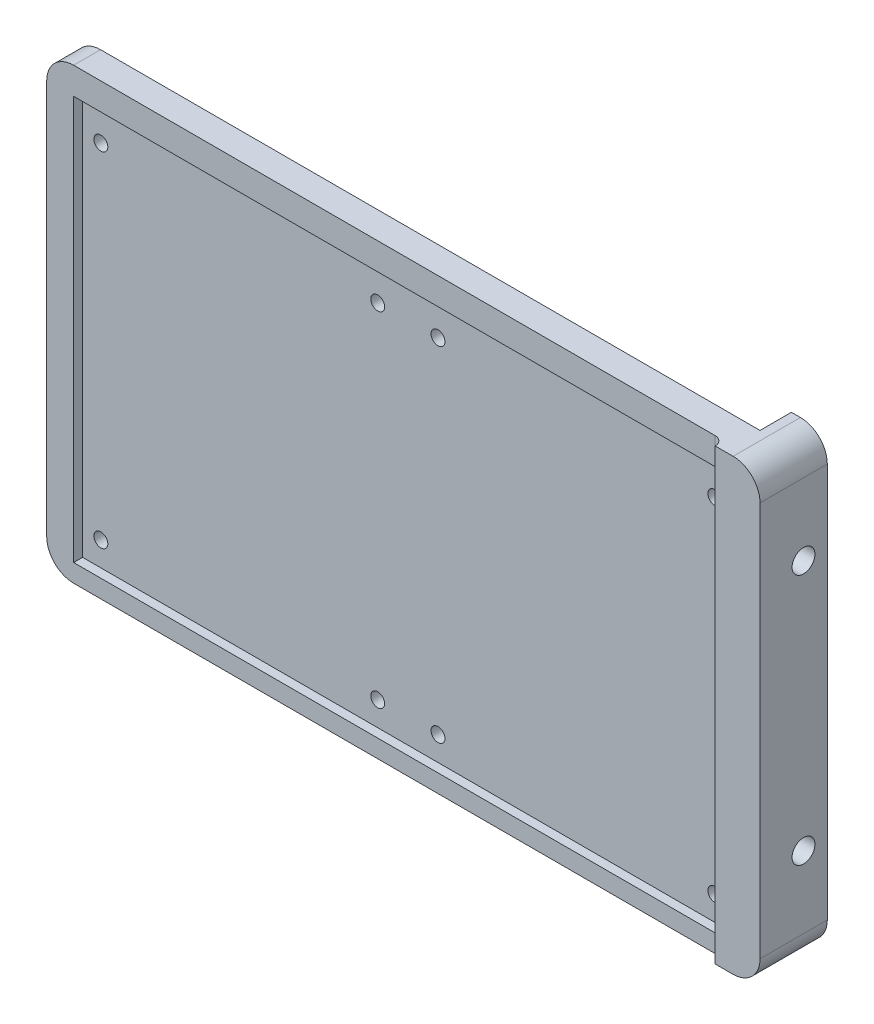
SolidWorks part; units mm, degrees
ref_plane "Front Plane" through (0, 0, 0) normal (0, 0, 1) x (1, 0, 0)
ref_plane "Top Plane" through (0, 0, 0) normal (0, 1, 0) x (1, 0, 0)
ref_plane "Right Plane" through (0, 0, 0) normal (1, 0, 0) x (0, 0, -1)
sketch "Sketch1" plane through (0, 0, 0) normal (0, 0, 1) x (1, 0, 0)
  line L0 (0, 0) -> (145, 0)
  line L1 (145, 0) -> (145, 100)
  line L2 (145, 100) -> (0, 100)
  line L3 (0, 100) -> (0, 0)
  line L4 (0, 0) -> (4.07, 0)
  line L5 (145, 0) -> (140.93, 0)
  line L6 (140.93, 0) -> (140.93, 100)
  line L7 (4.07, 0) -> (4.07, 100)
  line L8 (0, 100) -> (69.85, 100)
  line L9 (69.85, 100) -> (69.85, 0)
  line L10 (145, 100) -> (75.15, 100)
  line L11 (75.15, 100) -> (75.15, 0)
  line L12 (69.85, 100) -> (65.78, 100)
  line L13 (65.78, 100) -> (65.78, 0)
  line L14 (75.15, 100) -> (79.22, 100)
  line L15 (79.22, 100) -> (79.22, 0)
  line L16 (4.07, 100) -> (4.07, 86)
  line L17 (4.07, 86) -> (140.93, 86)
  line L18 (4.07, 100) -> (4.07, 9.4)
  line L19 (4.07, 9.4) -> (140.93, 9.4)
  circle A0 centre (4.07, 86) radius 1.55
  circle A1 centre (4.07, 9.4) radius 1.55
  circle A2 centre (65.78, 9.4) radius 1.55
  circle A3 centre (65.78, 86) radius 1.55
  circle A4 centre (79.22, 86) radius 1.55
  circle A5 centre (79.22, 9.4) radius 1.55
  circle A6 centre (140.93, 9.4) radius 1.55
  circle A7 centre (140.93, 86) radius 1.55
extrude "Boss-Extrude1" add sketch "Sketch1" along normal blind 4 contours A1 L18 A0 L2 L3 L0 L7 | A3 L13 L8 L18 A0 L17 | A3 L17 A0 L18 A1 L19 A2 L13 | A2 L19 A1 L7 L0 L13 | A3 L13 A2 L19 L9 L17 | L9 L19 L11 L17 | A5 L15 A4 L17 L11 L19 | A2 L13 L0 L9 L19 | L19 L9 L0 L11 | A5 L19 L11 L0 L15 | A3 L17 L9 L2 L13 | L9 L17 L11 L2 | A4 L15 L10 L11 L17 | A7 L6 L2 L15 A4 L17 | A7 L17 A4 L15 A5 L19 A6 L6 | A7 L6 A6 L0 L1 L2 | A6 L19 A5 L15 L0 L6 region at (2.009, 50.0435, 0) region at (34.925, 4.6735, 0) region at (67.8864, 4.4903, 0) region at (34.925, 93.0278, 0) region at (72.5, 4.7, 0) region at (34.925, 47.7, 0) region at (67.8622, 93.2172, 0) region at (77.1136, 4.4903, 0) region at (67.8319, 47.7, 0) region at (72.5, 47.7, 0) region at (72.5, 93, 0) region at (110.075, 4.6735, 0) region at (77.1681, 47.7, 0) region at (77.1378, 93.2172, 0) region at (142.991, 50.0435, 0) region at (110.075, 93.0278, 0) region at (110.075, 47.7, 0)
sketch "Sketch2" plane through (0, 100, 0) normal (0, 1, 0) x (1, 0, 0)
  line L0 (145, 0) -> (145, 7)
  line L1 (145, 7) -> (145, -10)
  line L2 (145, -10) -> (155, -10)
  line L3 (155, -10) -> (155, 7)
  line L4 (155, 7) -> (145, 7)
  line M4 (145, -4) -> (145, 0)
extrude "Boss-Extrude2" add sketch "Sketch2" against normal up to surface (100 mm away) contours L3 L4 L0 L1 L2 M4 region at (150, 100, 1.5) up to face at (72.5, 0, 2)
sketch "Sketch3" plane through (0, 0, 4) normal (0, 0, 1) x (1, 0, 0)
  line L0 (145, 100) -> (145, 94)
  line L1 (145, 0) -> (145, 100) construction
  line L2 (145, 100) -> (0, 100) construction
  line L3 (145, 94) -> (0, 94)
  line L4 (0, 100) -> (0, 0) construction
  line L5 (145, 0) -> (145, 4)
  line L6 (145, 4) -> (0, 4)
  line L7 (145, 0) -> (0, 0)
  line L8 (0, 0) -> (-6, 0)
  line L9 (-6, 0) -> (-6, 100)
  line L10 (-6, 100) -> (145, 100)
  line L11 (0, 94) -> (0, 4)
extrude "Boss-Extrude3" add sketch "Sketch3" along normal up to surface and the other way up to surface up to face at (150, 50, 10) other way up to face at (142.48, 86, 0)
fillet "Fillet1" radius 6 4 edges at (-6, 0, 5) (-6, 100, 5) (155, 0, 1.5) (155, 100, 1.5)
chamfer "Chamfer1" distance 2 angle 45 2 edges at (145, 0, -3.5) (145, 100, -3.5)
sketch "Sketch4" plane through (0, 0, 10) normal (0, 0, 1) x (1, 0, 0)
  line L4 (-6, 94) -> (-6, 6)
  line L5 (0, 0) -> (149, 0)
  line L6 (155, 6) -> (155, 94)
  line L7 (149, 100) -> (0, 100)
  line L8 (-6, 94) -> (-6, 6)
  line L9 (0, 0) -> (149, 0)
  line L10 (155, 6) -> (155, 94)
  line L11 (149, 100) -> (0, 100)
  arc A4 (-6, 6) -> (0, 0) centre (0, 6) ccw
  arc A5 (149, 0) -> (155, 6) centre (149, 6) ccw
  arc A6 (155, 94) -> (149, 100) centre (149, 94) ccw
  arc A7 (0, 100) -> (-6, 94) centre (0, 94) ccw
  arc A8 (-6, 6) -> (0, 0) centre (0, 6) ccw
  arc A9 (149, 0) -> (155, 6) centre (149, 6) ccw
  arc A10 (155, 94) -> (149, 100) centre (149, 94) ccw
  arc A11 (0, 100) -> (-6, 94) centre (0, 94) ccw
  dimension "D1" = 0
extrude "Cut-Extrude1" cut sketch "Sketch4" against normal blind 4
sketch "Sketch5" plane through (0, 0, 6) normal (0, 0, 1) x (1, 0, 0)
  line L0 (145, 94) -> (145, 100)
  line L1 (145, 100) -> (145, 0)
  line L4 (-6, 94) -> (-6, 6)
  line L5 (0, 0) -> (149, 0)
  line L6 (155, 6) -> (155, 94)
  line L7 (149, 100) -> (0, 100)
  line L8 (-6, 94) -> (-6, 6)
  line L9 (0, 0) -> (149, 0)
  line L10 (155, 6) -> (155, 94)
  line L11 (149, 100) -> (0, 100)
  arc A4 (0, 100) -> (-6, 94) centre (0, 94) ccw
  arc A5 (-6, 6) -> (0, 0) centre (0, 6) ccw
  arc A6 (149, 0) -> (155, 6) centre (149, 6) ccw
  arc A7 (155, 94) -> (149, 100) centre (149, 94) ccw
  arc A8 (0, 100) -> (-6, 94) centre (0, 94) ccw
  arc A9 (-6, 6) -> (0, 0) centre (0, 6) ccw
  arc A10 (149, 0) -> (155, 6) centre (149, 6) ccw
  arc A11 (155, 94) -> (149, 100) centre (149, 94) ccw
  line M12 (0, 0) -> (149, 0)
  arc M13 (149, 0) -> (155, 6) centre (149, 6) ccw
  line M14 (155, 6) -> (155, 94)
  arc M15 (155, 94) -> (149, 100) centre (149, 94) ccw
  line M16 (149, 100) -> (0, 100)
  line M17 (145, 94) -> (145, 4)
  dimension "D1" = 0
extrude "Boss-Extrude4" add sketch "Sketch5" along normal blind 2 contours L1 L0 M17 M12 M13 M14 M15 M16 region at (149.9426, 50, 6)
fillet "Fillet3" radius 2 2 edges at (145, 2, 6) (145, 97, 6)
sketch "Sketch6" plane through (155, 0, 0) normal (1, 0, 0) x (0, 0, -1)
  line L0 (7, 94) -> (1.7, 94)
  line L1 (7, 94) -> (-8, 94) construction
  line L2 (1.7, 94) -> (1.7, 6)
  line L3 (-8, 6) -> (7, 6) construction
  line L4 (1.7, 94) -> (1.7, 78)
  line L5 (1.7, 6) -> (1.7, 22)
  line L6 (1.7, 78) -> (1.7, 22)
  circle A0 centre (1.7, 78) radius 2.55
  circle A1 centre (1.7, 22) radius 2.55
extrude "Cut-Extrude2" cut sketch "Sketch6" against normal up to surface (10 mm away) contours L2 A0 L4 | L4 A0 L2 | L2 A1 | L2 A1 region at (155, 78, -2.7823) region at (155, 22, -2.7823) region at (155, 22, -0.6177) region at (155, 78, -0.6177)
fillet "Fillet4" radius 2 2 edges at (145, 22, 0) (145, 78, 0)
fillet "Fillet5" radius 2 4 edges at (144, 76.0993, 0) (144, 79.9007, 0) (144, 20.0993, 0) (144, 23.9007, 0)
